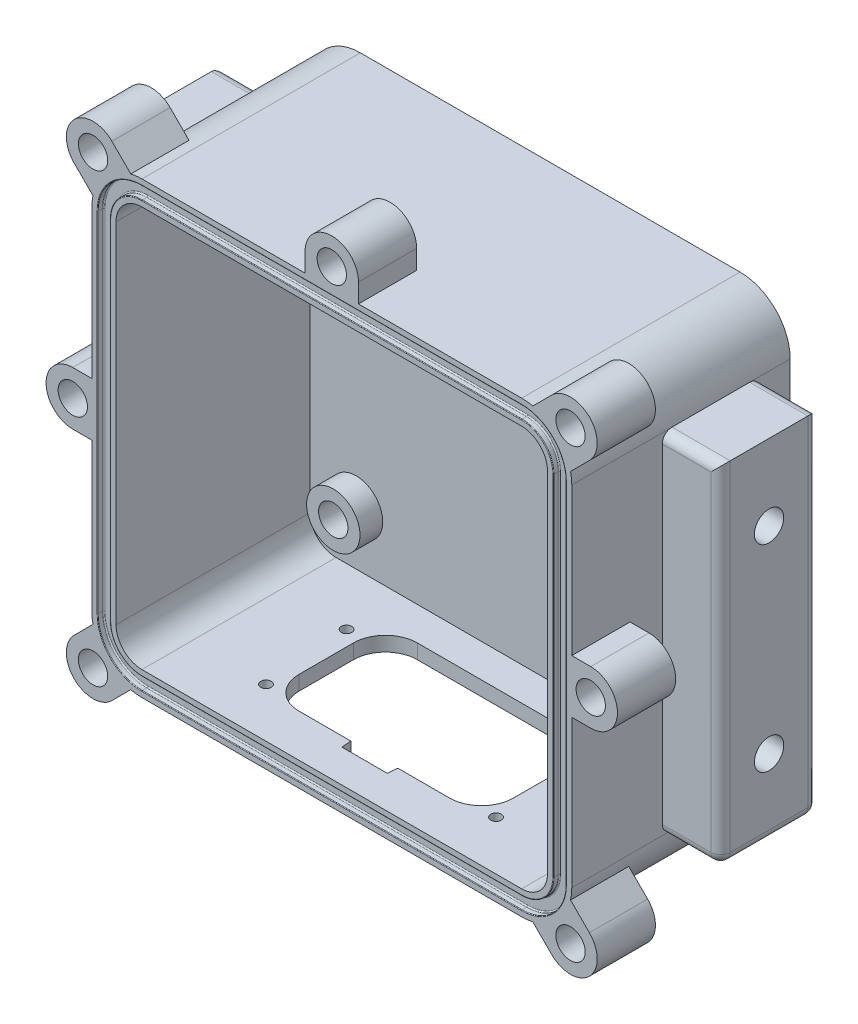
SolidWorks part; units mm, degrees
material "ABS"
ref_plane "X-Y Datum" through (0, 0, 0) normal (0, 0, 1) x (1, 0, 0)
ref_plane "X-Z Datum" through (0, 0, 0) normal (0, 1, 0) x (1, 0, 0)
ref_plane "Y-Z Datum" through (0, 0, 0) normal (1, 0, 0) x (0, 0, -1)
sketch "Sketch2" plane through (0, 0, 0) normal (0, 0, 1) x (1, 0, 0)
  line L5 (23.114, 67.818) -> (84.074, 67.818) construction
  line L6 (23.114, 67.818) -> (23.114, 122.428) construction
  line L7 (23.114, 122.428) -> (84.074, 122.428) construction
  line L8 (84.074, 67.818) -> (84.074, 122.428) construction
  line L9 (23.114, 67.818) -> (84.074, 122.428) construction
  line L10 (23.114, 122.428) -> (84.074, 67.818) construction
  line L14 (9.144, 136.398) -> (98.044, 136.398) construction
  line L15 (98.044, 53.848) -> (98.044, 136.398) construction
  line L16 (9.144, 53.848) -> (98.044, 53.848) construction
  line L17 (9.144, 53.848) -> (9.144, 136.398) construction
  line L18 (14.478, 136.398) -> (92.71, 136.398)
  line L19 (98.044, 59.182) -> (98.044, 131.064)
  line L20 (14.478, 53.848) -> (92.71, 53.848)
  line L21 (9.144, 59.182) -> (9.144, 131.064)
  line L22 (23.114, 95.123) -> (12.446, 95.123) construction
  line L23 (53.594, 67.818) -> (53.594, 60.198) construction
  line L24 (84.074, 95.123) -> (91.694, 95.123) construction
  line L25 (53.594, 122.428) -> (53.594, 130.048) construction
  line L26 (23.114, 122.428) -> (17.7258, 127.8162) construction
  circle A0 centre (25.292, 135.128) radius 2.1 construction
  circle A1 centre (51.708, 135.128) radius 2.1 construction
  circle A2 centre (79.14, 135.128) radius 2.1 construction
  circle A3 centre (51.708, 72.644) radius 2.1 construction
  circle A4 centre (79.14, 72.644) radius 2.1 construction
  circle A5 centre (25.292, 72.644) radius 2.1 construction
  arc A10 (92.71, 136.398) -> (98.044, 131.064) centre (92.71, 131.064) cw
  arc A11 (98.044, 59.182) -> (92.71, 53.848) centre (92.71, 59.182) cw
  arc A12 (14.478, 53.848) -> (9.144, 59.182) centre (14.478, 59.182) cw
  arc A13 (14.478, 136.398) -> (9.144, 131.064) centre (14.478, 131.064) ccw
  point P18 (53.594, 95.123)
  point P32 (20.066, 139.954)
  dimension "D2" = 82.55
  dimension "D1" = 5.334
  dimension "D4" = 88.9
  dimension "D3" = 13.97
extrude "Boss-Extrude1" add sketch "Sketch2" along normal blind 40
shell "Shell1" thickness 5 removed face at (53.594, 95.123, 40) outward yes
ref_plane "Plane1" through (53.594, 0, 0) normal (1, 0, 0) x (0, 0, -1)
ref_plane "Plane2" through (0, 95.123, 0) normal (0, -1, 0) x (-1, 0, 0)
sketch "Sketch15" plane through (0, 0, 40) normal (0, 0, 1) x (1, 0, 0)
  line L21 (92.71, 140.1807) -> (14.478, 140.1807)
  line L22 (5.3613, 131.064) -> (5.3613, 59.182)
  line L23 (14.478, 50.0653) -> (92.71, 50.0653)
  line L24 (101.8267, 59.182) -> (101.8267, 131.064)
  line L25 (92.71, 138.898) -> (14.478, 138.898)
  line L26 (6.644, 131.064) -> (6.644, 59.182)
  line L27 (14.478, 51.348) -> (92.71, 51.348)
  line L28 (100.544, 59.182) -> (100.544, 131.064)
  line L29 (92.71, 138.898) -> (14.478, 138.898) construction
  line L30 (6.644, 131.064) -> (6.644, 59.182) construction
  line L31 (14.478, 51.348) -> (92.71, 51.348) construction
  line L32 (100.544, 59.182) -> (100.544, 131.064) construction
  line L33 (7.9267, 131.064) -> (7.9267, 59.182)
  line L34 (14.478, 52.6307) -> (92.71, 52.6307)
  line L35 (99.2613, 59.182) -> (99.2613, 131.064)
  line L36 (92.71, 137.6153) -> (14.478, 137.6153)
  arc A17 (14.478, 140.1807) -> (5.3613, 131.064) centre (14.478, 131.064) ccw
  arc A18 (5.3613, 59.182) -> (14.478, 50.0653) centre (14.478, 59.182) ccw
  arc A19 (92.71, 50.0653) -> (101.8267, 59.182) centre (92.71, 59.182) ccw
  arc A20 (101.8267, 131.064) -> (92.71, 140.1807) centre (92.71, 131.064) ccw
  arc A21 (100.544, 131.064) -> (92.71, 138.898) centre (92.71, 131.064) ccw
  arc A22 (14.478, 138.898) -> (6.644, 131.064) centre (14.478, 131.064) ccw
  arc A23 (6.644, 59.182) -> (14.478, 51.348) centre (14.478, 59.182) ccw
  arc A24 (92.71, 51.348) -> (100.544, 59.182) centre (92.71, 59.182) ccw
  arc A25 (100.544, 131.064) -> (92.71, 138.898) centre (92.71, 131.064) ccw construction
  arc A26 (14.478, 138.898) -> (6.644, 131.064) centre (14.478, 131.064) ccw construction
  arc A27 (6.644, 59.182) -> (14.478, 51.348) centre (14.478, 59.182) ccw construction
  arc A28 (92.71, 51.348) -> (100.544, 59.182) centre (92.71, 59.182) ccw construction
  arc A29 (7.9267, 59.182) -> (14.478, 52.6307) centre (14.478, 59.182) ccw
  arc A30 (92.71, 52.6307) -> (99.2613, 59.182) centre (92.71, 59.182) ccw
  arc A31 (99.2613, 131.064) -> (92.71, 137.6153) centre (92.71, 131.064) ccw
  arc A32 (14.478, 137.6153) -> (7.9267, 131.064) centre (14.478, 131.064) ccw
  dimension "D4" = 6.5513
  dimension "D5" = 2.5654
  dimension "D1" = 2.5
  dimension "D2" = 1.2827
  dimension "D3" = 1.2827
extrude "Cut-Extrude4" cut sketch "Sketch15" against normal blind 1.2446
fillet "Fillet1" radius 0.254 16 edges at (97.3425, 54.5495, 38.7554) (53.594, 52.6307, 38.7554) (9.8455, 54.5495, 38.7554) (7.9267, 95.123, 38.7554) (9.8455, 135.6965, 38.7554) (53.594, 137.6153, 38.7554) (97.3425, 135.6965, 38.7554) (99.1565, 52.7355, 38.7554) (53.594, 50.0653, 38.7554) (8.0315, 52.7355, 38.7554) (5.3613, 95.123, 38.7554) (8.0315, 137.5105, 38.7554) (53.594, 140.1807, 38.7554) (99.1565, 137.5105, 38.7554) (99.2613, 95.123, 38.7554) (101.8267, 95.123, 38.7554)
fillet "Fillet2" radius 0.127 16 edges at (99.1565, 52.7355, 40) (53.594, 50.0653, 40) (8.0315, 52.7355, 40) (5.3613, 95.123, 40) (8.0315, 137.5105, 40) (53.594, 140.1807, 40) (99.1565, 137.5105, 40) (97.3425, 54.5495, 40) (53.594, 52.6307, 40) (9.8455, 54.5495, 40) (7.9267, 95.123, 40) (9.8455, 135.6965, 40) (53.594, 137.6153, 40) (97.3425, 135.6965, 40) (101.8267, 95.123, 40) (99.2613, 95.123, 40)
sketch "Sketch16" plane through (0, 0, 40) normal (0, 0, 1) x (1, 0, 0)
  line L0 (92.71, 59.182) -> (107.7852, 44.1068) construction
  line L1 (98.8927, 45.2211) -> (95.0072, 49.1066)
  line L2 (106.6709, 52.9993) -> (102.7854, 56.8848)
  arc A0 (92.71, 49.9383) -> (101.9537, 59.182) centre (92.71, 59.182) ccw construction
  circle A1 centre (102.7818, 49.1102) radius 3.025
  circle A2 centre (102.7818, 49.1102) radius 5.5
  arc A3 (92.71, 49.9383) -> (101.9537, 59.182) centre (92.71, 59.182) ccw
  arc A4 (92.71, 48.848) -> (103.044, 59.182) centre (92.71, 59.182) ccw construction
  point P3 (99.2463, 52.6457)
  arc M16 (92.71, 48.848) -> (103.044, 59.182) centre (92.71, 59.182) ccw
  arc M19 (101.9537, 59.182) -> (92.71, 49.9383) centre (92.71, 59.182) cw
  dimension "D2" = 11
  dimension "D3" = 6.05
  dimension "D1" = 5
extrude "Boss-Extrude7" add sketch "Sketch16" against normal blind 12 contours L0 A2 A1 M16 | L0 A1 A2 M16 | L0 A3 A2 M16 | L0 A2 M19 M16 | L0 A1 | A1 L0 | A2 L1 M16 | A2 L2 M16 region at (100.5309, 53.2679, 40) region at (98.6241, 51.3611, 40) region at (101.1901, 53.0599, 40) region at (100.2416, 51.4735, 40) region at (103.5584, 55.1802, 40) region at (96.7118, 48.3336, 40) region at (103.6896, 50.018, 40) region at (101.874, 48.2024, 40)
sketch "Sketch17" plane through (0, 0, 40) normal (0, 0, 1) x (1, 0, 0)
  circle A0 centre (102.7818, 49.1102) radius 3.025 construction
  circle A1 centre (102.7818, 49.1102) radius 3.025
  dimension "D1" = 6.05
extrude "Cut-Extrude5" cut sketch "Sketch17" against normal blind 9
mirror "Mirror2" about plane through (0, 95.123, 0) normal (0, -1, 0) of "Cut-Extrude5", "Boss-Extrude7"
mirror "Mirror3" about plane through (53.594, 0, 0) normal (1, 0, 0) of "Mirror2", "Cut-Extrude5", "Boss-Extrude7"
sketch "Sketch20" plane through (0, 0, 40) normal (0, 0, 1) x (1, 0, 0)
  line L0 (101.9537, 131.064) -> (101.9537, 59.182) construction
  line L1 (101.9537, 131.064) -> (101.9537, 59.182)
  line L2 (101.9537, 95.123) -> (119.767, 95.123) construction
  line L3 (106.9537, 89.623) -> (103.044, 89.623)
  line L4 (103.044, 59.182) -> (103.044, 131.064) construction
  line L5 (106.9537, 100.623) -> (103.044, 100.623)
  circle A0 centre (106.9537, 95.123) radius 3.025
  circle A1 centre (106.9537, 95.123) radius 5.5
  line M29 (103.044, 59.182) -> (103.044, 131.064)
  line M37 (101.9537, 131.064) -> (101.9537, 59.182)
  dimension "D1" = 6.05
  dimension "D2" = 11
  dimension "D3" = 5
extrude "Boss-Extrude9" add sketch "Sketch20" against normal blind 12 contours L2 A1 A0 M29 | L2 A0 A1 M29 | A1 L5 M29 | A1 L3 M29 | L2 A1 M37 M29 | L1 L2 A1 M29 | A0 L2 | L2 A0 region at (102.5431, 96.744, 40) region at (102.5431, 93.502, 40) region at (103.9901, 100.1491, 40) region at (107.6212, 98.1043, 40) region at (107.6212, 92.1417, 40) region at (103.9901, 90.0969, 40) region at (106.9537, 96.4069, 40) region at (106.9537, 93.8392, 40)
mirror "Mirror5" about plane through (53.594, 0, 0) normal (1, 0, 0) of "Boss-Extrude9"
sketch "Sketch22" plane through (4.144, 0, 0) normal (-1, 0, 0) x (0, 0, 1)
  line L0 (40, 95.123) -> (-5, 95.123) construction
  line L1 (40, 89.623) -> (40, 100.623) construction
  line L2 (-5, 131.064) -> (-5, 59.182) construction
  line L3 (40, 59.182) -> (-5, 59.182) construction
  line L4 (1.35, 131.064) -> (21.35, 131.064)
  line L5 (1.35, 131.064) -> (1.35, 59.182)
  line L6 (1.35, 59.182) -> (21.35, 59.182)
  line L7 (21.35, 131.064) -> (21.35, 59.182)
  line L8 (1.35, 131.064) -> (21.35, 59.182) construction
  line L9 (1.35, 59.182) -> (21.35, 131.064) construction
  line L12 (40, 131.064) -> (-5, 131.064) construction
  dimension "D1" = 6.35
  dimension "D2" = 20
extrude "Boss-Extrude10" add sketch "Sketch22" along normal blind 12
sketch "Sketch23" plane through (-7.856, 0, 0) normal (-1, 0, 0) x (0, 0, 1)
  line L0 (21.35, 95.123) -> (1.35, 95.123) construction
  line L1 (21.35, 59.182) -> (21.35, 131.064) construction
  line L2 (1.35, 131.064) -> (1.35, 59.182) construction
  line L3 (11.35, 58.848) -> (11.35, 131.064) construction
  line L5 (21.35, 131.064) -> (1.35, 131.064) construction
  circle A0 centre (11.35, 74.803) radius 3.025
  circle A1 centre (11.35, 115.443) radius 3.025
  dimension "D2" = 6.05
  dimension "D1" = 20.32
extrude "Cut-Extrude8" cut sketch "Sketch23" against normal blind 8
sketch "Sketch21" plane through (0, 0, 40) normal (0, 0, 1) x (1, 0, 0)
  circle A2 centre (0.2343, 95.123) radius 3.025
  dimension "D1" = 6.05
extrude "Cut-Extrude9" cut sketch "Sketch21" against normal blind 9
sketch "Sketch24" plane through (0, 48.848, 0) normal (0, -1, 0) x (1, 0, 0)
  line L0 (92.71, 40) -> (92.71, -5) construction
  line L1 (14.478, 40) -> (92.71, 40)
  line L2 (14.478, 40) -> (14.478, 28)
  line L3 (14.478, 28) -> (92.71, 28)
  line L4 (92.71, 40) -> (92.71, 28)
  dimension "D1" = 12
extrude "Boss-Extrude11" [suppressed] add sketch "Sketch24" along normal blind 16
sketch "Sketch26" [suppressed] plane through (0, 0, 25.4) normal (0, 0, 1) x (1, 0, 0)
  line L0 (18.378, 39.848) -> (92.71, 39.848) construction
  line L1 (18.378, 47.848) -> (92.71, 47.848)
  line L2 (18.378, 47.848) -> (18.378, 31.848)
  line L3 (18.378, 31.848) -> (92.71, 31.848)
  line L4 (92.71, 47.848) -> (92.71, 31.848)
  line L5 (55.544, 31.848) -> (55.544, 47.848) construction
  line L6 (18.378, 47.848) -> (55.544, 47.848)
  line L7 (55.544, 47.848) -> (36.961, 47.848)
  line L8 (36.961, 47.848) -> (36.961, 31.848) construction
  circle A2 centre (36.961, 39.848) radius 3.025
  circle A4 centre (74.127, 39.848) radius 3.025
  dimension "D1" = 6.05
extrude "Cut-Extrude11" [suppressed] cut sketch "Sketch26" against normal blind 9
mirror "Mirror6" [suppressed] about plane through (53.594, 0, 0) normal (1, 0, 0)
mirror "Mirror7" about plane through (53.594, 0, 0) normal (1, 0, 0) of "Cut-Extrude9", "Cut-Extrude8", "Boss-Extrude10"
fillet "Fillet3" radius 2 14 edges at (109.044, 59.182, 21.35) (109.044, 131.064, 21.35) (115.044, 95.123, 21.35) (-1.856, 131.064, 21.35) (-7.856, 95.123, 1.35) (-1.856, 59.182, 21.35) (-7.856, 95.123, 21.35) (-1.856, 131.064, 1.35) (109.044, 131.064, 1.35) (115.044, 59.182, 11.35) (109.044, 59.182, 1.35) (115.044, 95.123, 1.35) (-1.856, 59.182, 1.35) (-7.856, 59.182, 11.35)
sketch "Sketch27" plane through (0, 0, 0) normal (0, 0, 1) x (1, 0, 0)
  line L0 (20.719, 114.9979) -> (16.469, 114.9979)
  line L1 (70.4408, 114.9979) -> (106.7473, 114.9979) construction
  line L2 (20.719, 64.9979) -> (16.469, 64.9979) construction
  line L3 (90.719, 64.9979) -> (86.469, 64.9979) construction
  line L5 (90.719, 114.9979) -> (86.469, 114.9979) construction
  circle A0 centre (18.594, 114.9979) radius 3.025
  circle A1 centre (18.594, 114.9979) radius 5.5
  circle A2 centre (88.594, 114.9979) radius 3.025
  circle A3 centre (88.594, 114.9979) radius 5.5
  circle A4 centre (88.594, 64.9979) radius 3.025
  circle A5 centre (88.594, 64.9979) radius 5.5
  circle A6 centre (18.594, 64.9979) radius 3.025
  circle A7 centre (18.594, 64.9979) radius 5.5
  spline S3 degree 3 poles (90.719, 114.9979) (90.719, 119.2479) (86.469, 119.2479) (86.469, 114.9979) (86.469, 110.7479) (90.719, 110.7479) (90.719, 114.9979) (90.719, 119.2479) (86.469, 119.2479) knots -0.5 0 0 0 0.5 0.5 0.5 1 1 1 1.5 1.5 1.5 weights 1 0.333333 0.333333 1 0.333333 0.333333 1 0.333333 0.333333 only from (90.719, 114.9979) to (90.719, 114.9979) construction
  spline S4 degree 3 poles (20.719, 64.9979) (20.719, 69.2479) (16.469, 69.2479) (16.469, 64.9979) (16.469, 60.7479) (20.719, 60.7479) (20.719, 64.9979) (20.719, 69.2479) (16.469, 69.2479) knots -0.5 0 0 0 0.5 0.5 0.5 1 1 1 1.5 1.5 1.5 weights 1 0.333333 0.333333 1 0.333333 0.333333 1 0.333333 0.333333 only from (20.719, 64.9979) to (20.719, 64.9979) construction
  spline S6 degree 3 poles (90.719, 64.9979) (90.719, 69.2479) (86.469, 69.2479) (86.469, 64.9979) (86.469, 60.7479) (90.719, 60.7479) (90.719, 64.9979) (90.719, 69.2479) (86.469, 69.2479) knots -0.5 0 0 0 0.5 0.5 0.5 1 1 1 1.5 1.5 1.5 weights 1 0.333333 0.333333 1 0.333333 0.333333 1 0.333333 0.333333 only from (90.719, 64.9979) to (90.719, 64.9979) construction
  spline S8 degree 3 poles (20.719, 114.9979) (20.719, 119.2479) (16.469, 119.2479) (16.469, 114.9979) (16.469, 110.7479) (20.719, 110.7479) (20.719, 114.9979) (20.719, 119.2479) (16.469, 119.2479) knots -0.5 0 0 0 0.5 0.5 0.5 1 1 1 1.5 1.5 1.5 weights 1 0.333333 0.333333 1 0.333333 0.333333 1 0.333333 0.333333 only from (20.719, 114.9979) to (20.719, 114.9979)
  point P1 (18.594, 64.9979)
  point P2 (88.594, 64.9979)
  point P3 (18.594, 114.9979)
  point P5 (18.594, 114.9979)
  point P7 (88.594, 114.9979)
  point P9 (88.594, 64.9979)
  point P11 (18.594, 64.9979)
  point P24 (16.472, 115.2285)
  point P25 (88.594, 114.9979)
  dimension "D1" = 6.05
  dimension "D2" = 11
extrude "Boss-Extrude12" add sketch "Sketch27" along normal blind 4.69 contours A7 A6 | A1 A0 | A3 A2 | A5 A4 region at (13.2496, 114.9979, 0) region at (83.2496, 114.9979, 0) region at (83.2496, 64.9979, 0) region at (13.2496, 64.9979, 0)
sketch "Sketch28" plane through (0, 48.848, 0) normal (0, -1, 0) x (1, 0, 0)
  line L13 (51.0681, 33.231) -> (48.9199, 33.231)
  line L14 (48.9199, 33.231) -> (48.7144, 30.8832)
  line L15 (51.2735, 30.8832) -> (51.0681, 33.231)
  line L16 (51.0681, 33.231) -> (56.1199, 33.231)
  line L17 (50.894, 31.231) -> (55.9449, 31.231)
  line L18 (56.1199, 33.231) -> (55.9449, 31.231)
  line L19 (38.094, 31.231) -> (49.094, 31.231)
  line L20 (31.513, 13.45) -> (31.513, 24.65)
  line L21 (69.094, 6.869) -> (38.094, 6.869)
  line L22 (75.675, 24.65) -> (75.675, 13.45)
  line L23 (58.4431, 31.231) -> (69.094, 31.231)
  line L24 (58.4431, 31.231) -> (58.2681, 33.231)
  line L25 (56.1199, 33.231) -> (58.2681, 33.231)
  line L34 (24.594, 28.55) -> (24.594, 9.55)
  line L35 (31.594, 2.55) -> (75.594, 2.55)
  line L36 (82.594, 9.55) -> (82.594, 28.55)
  line L37 (75.594, 35.55) -> (31.594, 35.55)
  arc A12 (38.094, 31.231) -> (31.513, 24.65) centre (38.094, 24.65) ccw
  arc A13 (31.513, 13.45) -> (38.094, 6.869) centre (38.094, 13.45) ccw
  arc A14 (69.094, 6.869) -> (75.675, 13.45) centre (69.094, 13.45) ccw
  arc A15 (75.675, 24.65) -> (69.094, 31.231) centre (69.094, 24.65) ccw
  arc A16 (78.379, 29.85) -> (76.209, 29.85) centre (77.294, 29.85) ccw
  arc A17 (76.209, 29.85) -> (78.379, 29.85) centre (77.294, 29.85) ccw
  arc A18 (29.479, 11.75) -> (27.309, 11.75) centre (28.394, 11.75) ccw
  arc A19 (27.309, 11.75) -> (29.479, 11.75) centre (28.394, 11.75) ccw
  arc A20 (79.879, 11.75) -> (77.709, 11.75) centre (78.794, 11.75) ccw
  arc A21 (77.709, 11.75) -> (79.879, 11.75) centre (78.794, 11.75) ccw
  arc A22 (30.979, 29.85) -> (28.809, 29.85) centre (29.894, 29.85) ccw
  arc A23 (28.809, 29.85) -> (30.979, 29.85) centre (29.894, 29.85) ccw
  arc A32 (24.594, 9.55) -> (31.594, 2.55) centre (31.594, 9.55) ccw
  arc A33 (75.594, 2.55) -> (82.594, 9.55) centre (75.594, 9.55) ccw
  arc A34 (82.594, 28.55) -> (75.594, 35.55) centre (75.594, 28.55) ccw
  arc A35 (31.594, 35.55) -> (24.594, 28.55) centre (31.594, 28.55) ccw
extrude "Cut-Extrude12" cut sketch "Sketch28" against normal blind 5 contours A18 A19 | A22 A23 | A16 A17 | A20 A21 | L22 A15 L23 L24 L25 L18 L17 L15 L13 L14 L19 A12 L20 A13 L21 A14 | L18 L16 L15 L17 region at (53.594, 48.848, 19.1667) region at (53.594, 48.848, 32.243) region at (77.294, 48.848, 29.85) region at (28.394, 48.848, 11.75) region at (78.794, 48.848, 11.75) region at (29.894, 48.848, 29.85)
sketch "Sketch29" plane through (0, 48.848, 0) normal (0, -1, 0) x (1, 0, 0)
  line L0 (38.094, 31.231) -> (49.094, 31.231) construction
  line L1 (31.513, 13.45) -> (31.513, 24.65) construction
  line L2 (69.094, 6.869) -> (38.094, 6.869) construction
  line L3 (75.675, 24.65) -> (75.675, 13.45) construction
  line L4 (75.594, 35.55) -> (31.594, 35.55)
  line L5 (24.594, 28.55) -> (24.594, 9.55)
  line L6 (31.594, 2.55) -> (75.594, 2.55)
  line L7 (82.594, 9.55) -> (82.594, 28.55)
  line L8 (75.594, 35.55) -> (31.594, 35.55)
  line L9 (24.594, 28.55) -> (24.594, 9.55)
  line L10 (31.594, 2.55) -> (75.594, 2.55)
  line L11 (82.594, 9.55) -> (82.594, 28.55)
  line L12 (58.4431, 31.231) -> (69.094, 31.231) construction
  line L13 (58.4431, 31.231) -> (58.2681, 33.231) construction
  line L14 (56.1199, 33.231) -> (58.2681, 33.231) construction
  line L15 (51.0681, 33.231) -> (56.1199, 33.231) construction
  line L16 (56.1199, 33.231) -> (55.9449, 31.231) construction
  line L17 (50.894, 31.231) -> (55.9449, 31.231) construction
  line L18 (48.9199, 33.231) -> (48.7144, 30.8832) construction
  line L19 (51.0681, 33.231) -> (48.9199, 33.231) construction
  line L20 (51.2735, 30.8832) -> (51.0681, 33.231) construction
  line L21 (38.094, 31.231) -> (49.094, 31.231)
  line L22 (31.513, 13.45) -> (31.513, 24.65)
  line L23 (69.094, 6.869) -> (38.094, 6.869)
  line L24 (75.675, 24.65) -> (75.675, 13.45)
  line L25 (58.4431, 31.231) -> (69.094, 31.231)
  line L26 (58.4431, 31.231) -> (58.2681, 33.231)
  line L27 (56.1199, 33.231) -> (58.2681, 33.231)
  line L28 (51.0681, 33.231) -> (56.1199, 33.231)
  line L29 (56.1199, 33.231) -> (55.9449, 31.231)
  line L30 (50.894, 31.231) -> (55.9449, 31.231)
  line L31 (48.9199, 33.231) -> (48.7144, 30.8832)
  line L32 (51.0681, 33.231) -> (48.9199, 33.231)
  line L33 (51.2735, 30.8832) -> (51.0681, 33.231)
  arc A0 (38.094, 31.231) -> (31.513, 24.65) centre (38.094, 24.65) ccw construction
  arc A1 (31.513, 13.45) -> (38.094, 6.869) centre (38.094, 13.45) ccw construction
  arc A2 (29.479, 11.75) -> (27.309, 11.75) centre (28.394, 11.75) ccw
  arc A3 (27.309, 11.75) -> (29.479, 11.75) centre (28.394, 11.75) ccw
  arc A4 (29.479, 11.75) -> (27.309, 11.75) centre (28.394, 11.75) ccw
  arc A5 (27.309, 11.75) -> (29.479, 11.75) centre (28.394, 11.75) ccw
  arc A6 (78.379, 29.85) -> (76.209, 29.85) centre (77.294, 29.85) ccw
  arc A7 (76.209, 29.85) -> (78.379, 29.85) centre (77.294, 29.85) ccw
  arc A8 (78.379, 29.85) -> (76.209, 29.85) centre (77.294, 29.85) ccw
  arc A9 (76.209, 29.85) -> (78.379, 29.85) centre (77.294, 29.85) ccw
  arc A10 (30.979, 29.85) -> (28.809, 29.85) centre (29.894, 29.85) ccw
  arc A11 (28.809, 29.85) -> (30.979, 29.85) centre (29.894, 29.85) ccw
  arc A12 (31.594, 35.55) -> (24.594, 28.55) centre (31.594, 28.55) ccw
  arc A13 (24.594, 9.55) -> (31.594, 2.55) centre (31.594, 9.55) ccw
  arc A14 (75.594, 2.55) -> (82.594, 9.55) centre (75.594, 9.55) ccw
  arc A15 (82.594, 28.55) -> (75.594, 35.55) centre (75.594, 28.55) ccw
  arc A16 (31.594, 35.55) -> (24.594, 28.55) centre (31.594, 28.55) ccw
  arc A17 (24.594, 9.55) -> (31.594, 2.55) centre (31.594, 9.55) ccw
  arc A18 (75.594, 2.55) -> (82.594, 9.55) centre (75.594, 9.55) ccw
  arc A19 (82.594, 28.55) -> (75.594, 35.55) centre (75.594, 28.55) ccw
  arc A20 (30.979, 29.85) -> (28.809, 29.85) centre (29.894, 29.85) ccw
  arc A21 (28.809, 29.85) -> (30.979, 29.85) centre (29.894, 29.85) ccw
  arc A22 (79.879, 11.75) -> (77.709, 11.75) centre (78.794, 11.75) ccw
  arc A23 (77.709, 11.75) -> (79.879, 11.75) centre (78.794, 11.75) ccw
  arc A24 (79.879, 11.75) -> (77.709, 11.75) centre (78.794, 11.75) ccw
  arc A25 (77.709, 11.75) -> (79.879, 11.75) centre (78.794, 11.75) ccw
  arc A26 (69.094, 6.869) -> (75.675, 13.45) centre (69.094, 13.45) ccw construction
  arc A27 (75.675, 24.65) -> (69.094, 31.231) centre (69.094, 24.65) ccw construction
  arc A28 (38.094, 31.231) -> (31.513, 24.65) centre (38.094, 24.65) ccw
  arc A29 (31.513, 13.45) -> (38.094, 6.869) centre (38.094, 13.45) ccw
  arc A30 (69.094, 6.869) -> (75.675, 13.45) centre (69.094, 13.45) ccw
  arc A31 (75.675, 24.65) -> (69.094, 31.231) centre (69.094, 24.65) ccw
  circle M17 centre (29.894, 29.85) radius 1.085
  circle M18 centre (77.294, 29.85) radius 1.085
  circle M19 centre (78.794, 11.75) radius 1.085
  circle M24 centre (28.394, 11.75) radius 1.085
  line M27 (48.9199, 33.231) -> (58.2681, 33.231)
  line M28 (58.2681, 33.231) -> (58.4431, 31.231)
  line M29 (58.4431, 31.231) -> (69.094, 31.231)
  arc M30 (69.094, 31.231) -> (75.675, 24.65) centre (69.094, 24.65) cw
  line M31 (75.675, 24.65) -> (75.675, 13.45)
  arc M32 (75.675, 13.45) -> (69.094, 6.869) centre (69.094, 13.45) cw
  line M33 (69.094, 6.869) -> (38.094, 6.869)
  arc M34 (38.094, 6.869) -> (31.513, 13.45) centre (38.094, 13.45) cw
  line M35 (31.513, 13.45) -> (31.513, 24.65)
  arc M36 (31.513, 24.65) -> (38.094, 31.231) centre (38.094, 24.65) cw
  line M37 (38.094, 31.231) -> (48.7449, 31.231)
  line M38 (48.7449, 31.231) -> (48.9199, 33.231)
  line M39 (48.9199, 33.231) -> (58.2681, 33.231)
  dimension "D1" = 0
  dimension "D2" = 0
  dimension "D3" = 0
  dimension "D4" = 0
  dimension "D5" = 0
extrude "Cut-Extrude13" cut sketch "Sketch29" against normal blind 2 contours L11 A19 L8 A16 L9 A17 L10 A18 L28 M39 M27 M28 M29 M30 M31 M32 M33 M34 M35 M36 M37 M38 M17 M19 M24 M18 region at (80.0719, 48.848, 33.0279) body kept at (103.044, 131.064, 3.35)
sketch "Sketch30" plane through (0, 0, 40) normal (0, 0, 1) x (1, 0, 0)
  line L0 (53.594, 141.398) -> (53.594, 145.3077)
  line L3 (92.71, 141.398) -> (14.478, 141.398) construction
  line L4 (14.478, 140.3077) -> (92.71, 140.3077) construction
  line L5 (48.094, 145.3077) -> (48.094, 141.398)
  line L6 (48.094, 141.398) -> (59.094, 141.398)
  line L7 (59.094, 141.398) -> (59.094, 145.3077)
  circle A2 centre (53.594, 145.3077) radius 3.025
  circle A3 centre (53.594, 145.3077) radius 5.5
  line M5 (14.478, 140.3077) -> (92.71, 140.3077)
  line M37 (92.71, 141.398) -> (14.478, 141.398)
  dimension "D1" = 6.05
  dimension "D2" = 11
  dimension "D3" = 5
extrude "Boss-Extrude13" add sketch "Sketch30" against normal blind 12 contours A3 L7 M37 | A3 L5 L6 | A3 A2 L6 M37 | A2 | A3 L6 M37 M5 region at (51.5155, 147.3862, 40) region at (53.594, 140.8971, 40) region at (51.6598, 141.5428, 40) region at (48.5679, 142.3441, 40) region at (58.6201, 142.3441, 40)
sketch "Sketch31" plane through (0, 0, 40) normal (0, 0, 1) x (1, 0, 0)
  circle A0 centre (53.594, 145.3077) radius 3.025 construction
  circle A1 centre (53.594, 145.3077) radius 3.025
  dimension "D1" = 6.05
extrude "Cut-Extrude14" cut sketch "Sketch31" against normal blind 9
sketch "Sketch33" plane through (0, 0, 4.69) normal (0, 0, 1) x (1, 0, 0)
  circle A0 centre (88.594, 64.9979) radius 3.025 construction
  circle A1 centre (88.594, 114.9979) radius 3.025 construction
  circle A2 centre (18.594, 114.9979) radius 3.025 construction
  circle A3 centre (18.594, 64.9979) radius 3.025 construction
  circle A4 centre (88.594, 64.9979) radius 3.025
  circle A5 centre (88.594, 114.9979) radius 3.025
  circle A6 centre (18.594, 114.9979) radius 3.025
  circle A7 centre (18.594, 64.9979) radius 3.025
extrude "Cut-Extrude15" cut sketch "Sketch33" against normal blind 5
